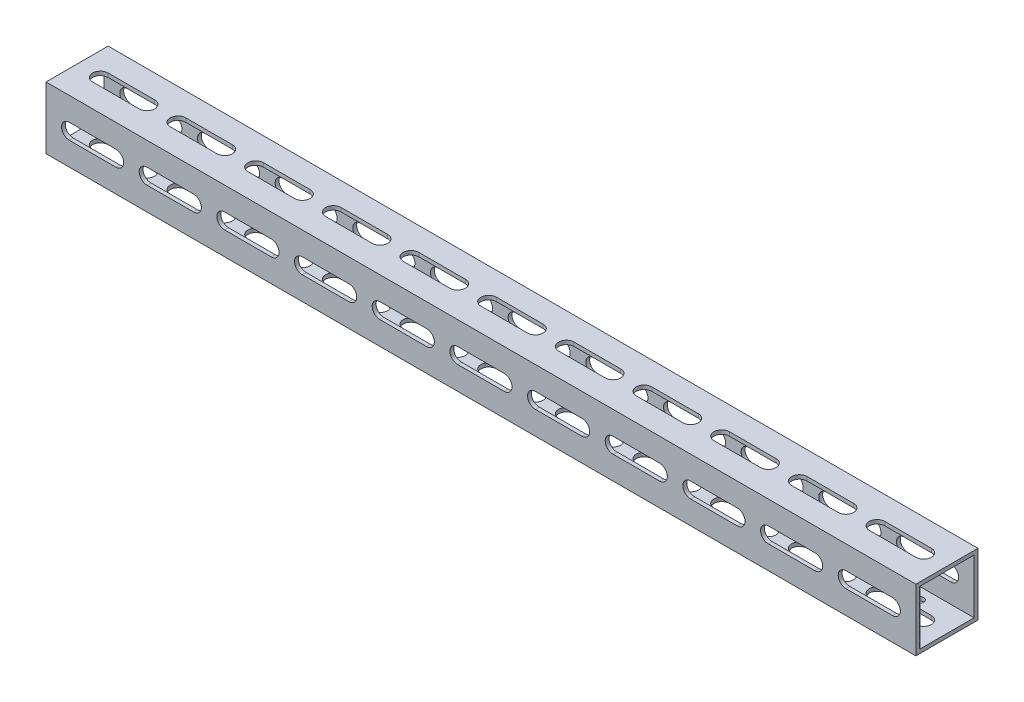
SolidWorks part; units mm, degrees
material "6061-T6 (SS)"
ref_plane "Front" through (0, 0, 0) normal (0, 0, 1) x (1, 0, 0)
ref_plane "Top" through (0, 0, 0) normal (0, 1, 0) x (1, 0, 0)
ref_plane "Right" through (0, 0, 0) normal (1, 0, 0) x (0, 0, -1)
sketch "Sketch1" plane through (0, 0, 0) normal (1, 0, 0) x (0, 0, -1)
  line L1 (-12.7, -12.7) -> (12.7, -12.7)
  line L2 (-12.7, -12.7) -> (-12.7, 12.7)
  line L3 (-12.7, 12.7) -> (12.7, 12.7)
  line L4 (12.7, -12.7) -> (12.7, 12.7)
  line L5 (-12.7, -12.7) -> (12.7, 12.7) construction
  line L6 (-12.7, 12.7) -> (12.7, -12.7) construction
  point P0 (0, 0)
  dimension "D1" = 25.4
extrude "Extrude-Thin1" add sketch "Sketch1" along normal up to surface (355.6 mm away) thin thin type one direction reverse wall 1.5875
sketch "Sketch4" plane through (0, -12.7, 0) normal (0, -1, 0) x (1, 0, 0)
  line L0 (0, 12.7) -> (0, -12.7) construction
  line L2 (17.4625, -6.35) -> (0, 0) construction
  line L3 (0, 0) -> (17.4625, 6.35) construction
  line L4 (177.8, -12.7) -> (177.8, 38.5816) construction
  line L5 (355.6, -12.7) -> (0, -12.7) construction
  point P0 (17.4625, -6.35)
  point P2 (26.9875, 6.35)
  point P7 (26.9875, -6.35)
  point P10 (17.4625, 6.35)
  point P22 (71.4375, -6.35)
  point P24 (61.9125, -6.35)
  point P26 (61.9125, 6.35)
  point P28 (71.4375, 6.35)
  point P37 (284.1625, 6.35)
  point P38 (293.6875, 6.35)
  point P39 (293.6875, -6.35)
  point P40 (284.1625, -6.35)
  point P41 (338.1375, 6.35)
  point P42 (328.6125, -6.35)
  point P43 (328.6125, 6.35)
  point P44 (338.1375, -6.35)
  dimension "D1" = 17.4625
  dimension "D2" = 9.525
  dimension "D3" = 12.7
  dimension "D4" = 44.45
  dimension "D5" = 9.525
hole_wizard "#30 (0.13) Diameter Hole1" positions "Sketch4" profile "Sketch3" hole size "#30" standard "ANSI Inch" end condition up to next
sketch "Sketch3" plane through (17.4625, -12.7, -6.35) normal (1, 0, 0) x (0, 0, -1)
  line L0 (0, 0) -> (0, 1.5875)
  line L1 (0, 1.5875) -> (1.651, 1.5875)
  line L2 (1.651, 1.5875) -> (1.651, 0)
  line L5 (1.651, 0) -> (0, 0)
  line L11 (0, -6.35) -> (0, 107.95) construction
  dimension "Thru Hole Dia." = 3.302
  dimension "Thru Hole Depth" = 1.5875
sketch "Sketch5" plane through (0, 12.7, 0) normal (0, 1, 0) x (1, 0, 0)
  line L0 (9.525, 0) -> (28.575, 0) construction
  line L1 (9.525, 3.175) -> (28.575, 3.175)
  line L2 (9.525, -3.175) -> (28.575, -3.175)
  line L3 (0, 12.7) -> (0, -12.7) construction
  line L4 (41.275, 0) -> (60.325, 0) construction
  line L5 (41.275, 3.175) -> (60.325, 3.175)
  line L6 (41.275, -3.175) -> (60.325, -3.175)
  line L7 (73.025, 0) -> (92.075, 0) construction
  line L8 (73.025, 3.175) -> (92.075, 3.175)
  line L9 (73.025, -3.175) -> (92.075, -3.175)
  line L10 (104.775, 0) -> (123.825, 0) construction
  line L11 (104.775, 3.175) -> (123.825, 3.175)
  line L12 (104.775, -3.175) -> (123.825, -3.175)
  line L13 (136.525, 0) -> (155.575, 0) construction
  line L14 (136.525, 3.175) -> (155.575, 3.175)
  line L15 (136.525, -3.175) -> (155.575, -3.175)
  line L16 (168.275, 0) -> (187.325, 0) construction
  line L17 (168.275, 3.175) -> (187.325, 3.175)
  line L18 (168.275, -3.175) -> (187.325, -3.175)
  line L19 (200.025, 0) -> (219.075, 0) construction
  line L20 (200.025, 3.175) -> (219.075, 3.175)
  line L21 (200.025, -3.175) -> (219.075, -3.175)
  line L22 (231.775, 0) -> (250.825, 0) construction
  line L23 (231.775, 3.175) -> (250.825, 3.175)
  line L24 (231.775, -3.175) -> (250.825, -3.175)
  line L25 (263.525, 0) -> (282.575, 0) construction
  line L26 (263.525, 3.175) -> (282.575, 3.175)
  line L27 (263.525, -3.175) -> (282.575, -3.175)
  line L28 (295.275, 0) -> (314.325, 0) construction
  line L29 (295.275, 3.175) -> (314.325, 3.175)
  line L30 (295.275, -3.175) -> (314.325, -3.175)
  line L31 (327.025, 0) -> (346.075, 0) construction
  line L32 (327.025, 3.175) -> (346.075, 3.175)
  line L33 (327.025, -3.175) -> (346.075, -3.175)
  arc A0 (9.525, 3.175) -> (9.525, -3.175) centre (9.525, 0) ccw
  arc A1 (28.575, -3.175) -> (28.575, 3.175) centre (28.575, 0) ccw
  arc A2 (41.275, 3.175) -> (41.275, -3.175) centre (41.275, 0) ccw
  arc A3 (60.325, -3.175) -> (60.325, 3.175) centre (60.325, 0) ccw
  arc A4 (73.025, 3.175) -> (73.025, -3.175) centre (73.025, 0) ccw
  arc A5 (92.075, -3.175) -> (92.075, 3.175) centre (92.075, 0) ccw
  arc A6 (104.775, 3.175) -> (104.775, -3.175) centre (104.775, 0) ccw
  arc A7 (123.825, -3.175) -> (123.825, 3.175) centre (123.825, 0) ccw
  arc A8 (136.525, 3.175) -> (136.525, -3.175) centre (136.525, 0) ccw
  arc A9 (155.575, -3.175) -> (155.575, 3.175) centre (155.575, 0) ccw
  arc A10 (168.275, 3.175) -> (168.275, -3.175) centre (168.275, 0) ccw
  arc A11 (187.325, -3.175) -> (187.325, 3.175) centre (187.325, 0) ccw
  arc A12 (200.025, 3.175) -> (200.025, -3.175) centre (200.025, 0) ccw
  arc A13 (219.075, -3.175) -> (219.075, 3.175) centre (219.075, 0) ccw
  arc A14 (231.775, 3.175) -> (231.775, -3.175) centre (231.775, 0) ccw
  arc A15 (250.825, -3.175) -> (250.825, 3.175) centre (250.825, 0) ccw
  arc A16 (263.525, 3.175) -> (263.525, -3.175) centre (263.525, 0) ccw
  arc A17 (282.575, -3.175) -> (282.575, 3.175) centre (282.575, 0) ccw
  arc A18 (295.275, 3.175) -> (295.275, -3.175) centre (295.275, 0) ccw
  arc A19 (314.325, -3.175) -> (314.325, 3.175) centre (314.325, 0) ccw
  arc A20 (327.025, 3.175) -> (327.025, -3.175) centre (327.025, 0) ccw
  arc A21 (346.075, -3.175) -> (346.075, 3.175) centre (346.075, 0) ccw
  point P2 (19.05, 0)
  point P13 (50.8, 0)
  point P20 (82.55, 0)
  point P27 (114.3, 0)
  point P34 (146.05, 0)
  point P41 (177.8, 0)
  point P48 (209.55, 0)
  point P55 (241.3, 0)
  point P62 (273.05, 0)
  point P69 (304.8, 0)
  point P76 (336.55, 0)
  dimension "D3" = 9.525
  dimension "D5" = 12.7
  dimension "D1" = 6.35
  dimension "D2" = 19.05
  dimension "D4" = 11
extrude "Cut-Extrude1" cut sketch "Sketch5" against normal through all
sketch "Sketch6" plane through (0, 0, 12.7) normal (0, 0, 1) x (1, 0, 0)
  line L0 (9.525, 0) -> (28.575, 0) construction
  line L1 (9.525, 3.175) -> (28.575, 3.175)
  line L2 (9.525, -3.175) -> (28.575, -3.175)
  line L3 (0, 12.7) -> (0, -12.7) construction
  line L4 (41.275, 0) -> (60.325, 0) construction
  line L5 (41.275, 3.175) -> (60.325, 3.175)
  line L6 (41.275, -3.175) -> (60.325, -3.175)
  line L7 (73.025, 0) -> (92.075, 0) construction
  line L8 (73.025, 3.175) -> (92.075, 3.175)
  line L9 (73.025, -3.175) -> (92.075, -3.175)
  line L10 (104.775, 0) -> (123.825, 0) construction
  line L11 (104.775, 3.175) -> (123.825, 3.175)
  line L12 (104.775, -3.175) -> (123.825, -3.175)
  line L13 (136.525, 0) -> (155.575, 0) construction
  line L14 (136.525, 3.175) -> (155.575, 3.175)
  line L15 (136.525, -3.175) -> (155.575, -3.175)
  line L16 (168.275, 0) -> (187.325, 0) construction
  line L17 (168.275, 3.175) -> (187.325, 3.175)
  line L18 (168.275, -3.175) -> (187.325, -3.175)
  line L19 (200.025, 0) -> (219.075, 0) construction
  line L20 (200.025, 3.175) -> (219.075, 3.175)
  line L21 (200.025, -3.175) -> (219.075, -3.175)
  line L22 (231.775, 0) -> (250.825, 0) construction
  line L23 (231.775, 3.175) -> (250.825, 3.175)
  line L24 (231.775, -3.175) -> (250.825, -3.175)
  line L25 (263.525, 0) -> (282.575, 0) construction
  line L26 (263.525, 3.175) -> (282.575, 3.175)
  line L27 (263.525, -3.175) -> (282.575, -3.175)
  line L28 (295.275, 0) -> (314.325, 0) construction
  line L29 (295.275, 3.175) -> (314.325, 3.175)
  line L30 (295.275, -3.175) -> (314.325, -3.175)
  line L31 (327.025, 0) -> (346.075, 0) construction
  line L32 (327.025, 3.175) -> (346.075, 3.175)
  line L33 (327.025, -3.175) -> (346.075, -3.175)
  arc A0 (9.525, 3.175) -> (9.525, -3.175) centre (9.525, 0) ccw
  arc A1 (28.575, -3.175) -> (28.575, 3.175) centre (28.575, 0) ccw
  arc A2 (41.275, 3.175) -> (41.275, -3.175) centre (41.275, 0) ccw
  arc A3 (60.325, -3.175) -> (60.325, 3.175) centre (60.325, 0) ccw
  arc A4 (73.025, 3.175) -> (73.025, -3.175) centre (73.025, 0) ccw
  arc A5 (92.075, -3.175) -> (92.075, 3.175) centre (92.075, 0) ccw
  arc A6 (104.775, 3.175) -> (104.775, -3.175) centre (104.775, 0) ccw
  arc A7 (123.825, -3.175) -> (123.825, 3.175) centre (123.825, 0) ccw
  arc A8 (136.525, 3.175) -> (136.525, -3.175) centre (136.525, 0) ccw
  arc A9 (155.575, -3.175) -> (155.575, 3.175) centre (155.575, 0) ccw
  arc A10 (168.275, 3.175) -> (168.275, -3.175) centre (168.275, 0) ccw
  arc A11 (187.325, -3.175) -> (187.325, 3.175) centre (187.325, 0) ccw
  arc A12 (200.025, 3.175) -> (200.025, -3.175) centre (200.025, 0) ccw
  arc A13 (219.075, -3.175) -> (219.075, 3.175) centre (219.075, 0) ccw
  arc A14 (231.775, 3.175) -> (231.775, -3.175) centre (231.775, 0) ccw
  arc A15 (250.825, -3.175) -> (250.825, 3.175) centre (250.825, 0) ccw
  arc A16 (263.525, 3.175) -> (263.525, -3.175) centre (263.525, 0) ccw
  arc A17 (282.575, -3.175) -> (282.575, 3.175) centre (282.575, 0) ccw
  arc A18 (295.275, 3.175) -> (295.275, -3.175) centre (295.275, 0) ccw
  arc A19 (314.325, -3.175) -> (314.325, 3.175) centre (314.325, 0) ccw
  arc A20 (327.025, 3.175) -> (327.025, -3.175) centre (327.025, 0) ccw
  arc A21 (346.075, -3.175) -> (346.075, 3.175) centre (346.075, 0) ccw
  point P3 (19.05, 0)
  point P13 (50.8, 0)
  point P20 (82.55, 0)
  point P27 (114.3, 0)
  point P34 (146.05, 0)
  point P41 (177.8, 0)
  point P48 (209.55, 0)
  point P55 (241.3, 0)
  point P62 (273.05, 0)
  point P69 (304.8, 0)
  point P76 (336.55, 0)
  dimension "D3" = 9.525
  dimension "D5" = 12.7
  dimension "D1" = 6.35
  dimension "D2" = 19.05
  dimension "D4" = 11
extrude "Cut-Extrude2" cut sketch "Sketch6" against normal through all
